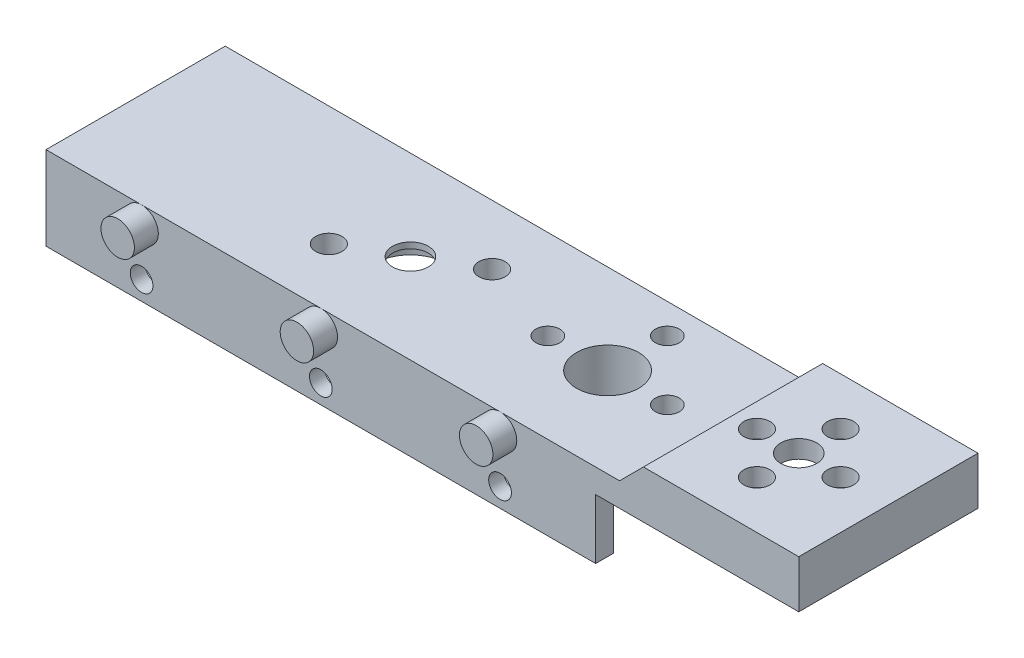
SolidWorks part; units mm, degrees
note: The reader was unsure of these and kept them because the rebuilt part matched: shared geometry of "草图2<3>", "草图1<7>", "草图1<8>".
ref_plane "前视基准面" through (0, 0, 0) normal (0, 0, 1) x (1, 0, 0)
ref_plane "上视基准面" through (0, 0, 0) normal (0, 1, 0) x (1, 0, 0)
ref_plane "右视基准面" through (0, 0, 0) normal (1, 0, 0) x (0, 0, -1)
other "Configuration Table"
sketch "草图1" plane through (0, 0, 0) normal (0, 1, 0) x (1, 0, 0)
  line L0 (-31.5, 7.5) -> (31.5, 7.5)
  line L1 (31.5, 7.5) -> (31.5, -7.5)
  line L2 (31.5, -7.5) -> (-31.5, -7.5)
  line L3 (-31.5, -7.5) -> (-31.5, 7.5)
  line L4 (-31.5, 0) -> (31.5, 0) construction
  line L5 (-12.8301, -2.5) -> (-4.1699, 2.5) construction
  line L6 (-13.3083, -5.95) -> (-3.6917, -5.95) construction
  line L7 (-13.3083, 5.95) -> (-3.6917, 5.95) construction
  line L8 (-8.5, 0) -> (-8.5, 4.4384) construction
  line L10 (31.5, 7.5) -> (16.5, 7.5)
  line L11 (31.5, 7.5) -> (31.5, -7.5)
  line L12 (31.5, -7.5) -> (16.5, -7.5)
  line L13 (16.5, 7.5) -> (16.5, -7.5)
  circle A0 centre (-8.5, 0) radius 1.5
  circle A1 centre (-4.1699, 2.5) radius 1.1
  circle A3 centre (-12.8301, -2.5) radius 1.1
  arc A4 (-13.3083, 5.95) -> (-13.3083, -5.95) centre (-8.5, 0) ccw construction
  circle A5 centre (8, 0) radius 2.6
  arc A6 (-3.6917, -5.95) -> (-3.6917, 5.95) centre (-8.5, 0) ccw construction
  circle A7 centre (24, 0) radius 1.5
  circle A8 centre (24, 0) radius 3.5 construction
  circle A9 centre (27.5, 0) radius 1.1
  circle A10 centre (24, -3.5) radius 1.1
  circle A11 centre (20.5, 0) radius 1.1
  circle A12 centre (24, 3.5) radius 1.1
  circle A13 centre (-4.1699, -2.5) radius 1.1
  circle A14 centre (-12.8301, 2.5) radius 1.1
  circle A15 centre (13, 0) radius 1
  circle A17 centre (3, 0) radius 1
  circle A18 centre (8, 5) radius 1
  circle A19 centre (8, -5) radius 1 [skipped]
  circle A20 centre (24, 0) radius 6
  point P5 (0, 7.5)
  point P7 (-31.5, 0)
  dimension "D3" = 3
  dimension "D6" = 2.2
  dimension "D9" = 15.3
  dimension "D12" = 5.2
  dimension "D14" = 3
  dimension "D15" = 7
  dimension "D16" = 2.2
  dimension "D18" = 2
  dimension "D22" = 12
  dimension "D1" = 63
  dimension "D2" = 15
  dimension "D4" = 23
  dimension "D7" = 30
  dimension "D8" = 10
  dimension "D10" = 11.9
  dimension "D11" = 16.5
  dimension "D13" = 16
  dimension "D19" = 5
  dimension "D21" = 15
  dimension "D5" = 2
  dimension "D17" = 4
  dimension "D20" = 4
extrude "凸台-拉伸1" add sketch "草图1" along normal blind 2 contours A3 | L3 L2 L1 L0 A13 A12 A11 A10 A9 A7 A5 A3 A1 A0 A14 | A1 | L11 L10 L13 L12
sketch "草图2" plane through (0, 0, 7.5) normal (0, 0, 1) x (1, 0, 0)
  line L0 (-31, 0.6) -> (31, 0.6) construction
  line L1 (-31.5, 2) -> (-31.5, 0) construction
  line L3 (31.5, 2) -> (-31.5, 2) construction
  circle A0 centre (-23.5, 0.6) radius 1.4
  circle A1 centre (-8.5, 0.6) radius 1.4
  circle A2 centre (6.5, 0.6) radius 1.4
  circle A3 centre (-23.5, -3.4) radius 0.95
  circle A4 centre (-8.5, -3.4) radius 0.95
  circle A5 centre (6.5, -3.4) radius 0.95
  line M13 (-31.5, 0) -> (31.5, 0)
  dimension "D1" = 2.8
  dimension "D2" = 2.8
  dimension "D3" = 2.8
  dimension "D8" = 1.9
  dimension "D4" = 15
  dimension "D5" = 15
  dimension "D6" = 8
  dimension "D7" = 1.4
  dimension "D9" = 4
  dimension "D10" = 3
extrude "凸台-拉伸2" add sketch "草图2" along normal blind 2 contours A0 L0 | L0 A0 M13 | A0 M13 | A1 L0 | L0 A1 M13 | A2 L0 | L0 A2 M13 | A2 M13
sketch "草图3" plane through (0, 0, 0) normal (0, -1, 0) x (1, 0, 0)
  circle A0 centre (-8.5, 0) radius 3
  dimension "D1" = 6
extrude "切除-拉伸1" cut sketch "草图3" against normal blind 1.5
sketch "草图4" plane through (0, 0, 0) normal (0, -1, 0) x (1, 0, 0)
  line L1 (-31.5, 7.5) -> (14.5, 7.5)
  line L2 (-31.5, 7.5) -> (-31.5, 6)
  line L3 (-31.5, 6) -> (14.5, 6)
  line L4 (14.5, 7.5) -> (14.5, 6)
  dimension "D1" = 46
  dimension "D2" = 1.5
extrude "凸台-拉伸3" add sketch "草图4" along normal blind 5
extrude "切除-拉伸2" cut sketch "草图2<3>" against normal up to surface (1.5 mm away) contours A3 | A4 | A5 up to face at (-8.5, -2.5, 6)
sketch "草图2<3>" plane through (0, 0, 7.5) normal (0, 0, 1) x (1, 0, 0) same geometry as "草图2"
sketch "草图5" plane through (0, 0, 6) normal (0, 0, -1) x (-1, 0, 0)
  line L0 (22.403, -1.5) -> (24.597, -1.5)
  line L1 (24.597, -1.5) -> (25.6939, -3.4)
  line L2 (25.6939, -3.4) -> (24.597, -5.3)
  line L3 (24.597, -5.3) -> (22.403, -5.3)
  line L4 (22.403, -5.3) -> (21.3061, -3.4)
  line L5 (21.3061, -3.4) -> (22.403, -1.5)
  line L6 (21.3061, -3.4) -> (25.6939, -3.4) construction
  line L7 (24.597, -1.5) -> (22.403, -5.3) construction
  line L8 (6.3061, -3.4) -> (7.403, -1.5)
  line L9 (7.403, -1.5) -> (9.597, -1.5)
  line L10 (9.597, -1.5) -> (10.6939, -3.4)
  line L11 (10.6939, -3.4) -> (9.597, -5.3)
  line L12 (9.597, -5.3) -> (7.403, -5.3)
  line L13 (7.403, -5.3) -> (6.3061, -3.4)
  line L14 (-8.6939, -3.4) -> (-7.597, -1.5)
  line L15 (-7.597, -1.5) -> (-5.403, -1.5)
  line L16 (-5.403, -1.5) -> (-4.3061, -3.4)
  line L17 (-4.3061, -3.4) -> (-5.403, -5.3)
  line L18 (-5.403, -5.3) -> (-7.597, -5.3)
  line L19 (-7.597, -5.3) -> (-8.6939, -3.4)
  line L20 (7.403, -1.5) -> (9.597, -5.3) construction
  line L21 (7.403, -5.3) -> (9.597, -1.5) construction
  circle A0 centre (23.5, -3.4) radius 0.95
  circle A1 centre (8.5, -3.4) radius 0.95
  circle A2 centre (8.5, -3.4) radius 0.95 construction
  circle A3 centre (23.5, -3.4) radius 0.95 construction
  point P17 (23.5, -3.4)
  dimension "D1" = 120
  dimension "D2" = 120
  dimension "D3" = 120
  dimension "D4" = 3.8
  dimension "D5" = 3.8
  dimension "D6" = 3.8
  dimension "D7" = 3
extrude "切除-拉伸3" cut sketch "草图5" against normal blind 0.25 contours L14 L15 L16 L17 L18 L19 | L8 L9 L10 L11 L12 L13 | L5 L0 L1 L2 L3 L4
extrude "凸台-拉伸4" add sketch "草图1<7>" along normal blind 4 contours L11 L10 L13 L12 | A12 | A9 | A10 | A7 | A11
sketch "草图1<7>" plane through (0, 0, 0) normal (0, 1, 0) x (1, 0, 0) same geometry as "草图1"
extrude "切除-拉伸4" cut sketch "草图1<8>" along normal blind 2.5 contours A20 A7 A9 A10 A11 A12
sketch "草图1<8>" plane through (0, 0, 0) normal (0, 1, 0) x (1, 0, 0) same geometry as "草图1"
sketch "草图6" plane through (0, 0, -7.5) normal (0, 0, -1) x (-1, 0, 0)
  line L0 (-16.5, 2) -> (-18.5, 4)
  line L1 (-31.5, 4) -> (-16.5, 4) construction
  line L2 (-18.5, 4) -> (-16.5, 4)
  line L3 (-16.5, 4) -> (-16.5, 2) construction
  line L4 (-16.5, 4) -> (-16.5, 2)
  dimension "D1" = 45
extrude "切除-拉伸5" cut sketch "草图6" against normal up to surface (15 mm away) up to face at (1.0857, 0.7, 7.5)
sketch "草图8" plane through (0, 0, 0) normal (0, -1, 0) x (1, 0, 0)
  circle A0 centre (8, 0) radius 2.6
  circle A1 centre (8, 0) radius 3.6
  circle A2 centre (8, 0) radius 2.6 construction
  dimension "D1" = 7.2
extrude "凸台-拉伸5" add sketch "草图8" along normal blind 2
